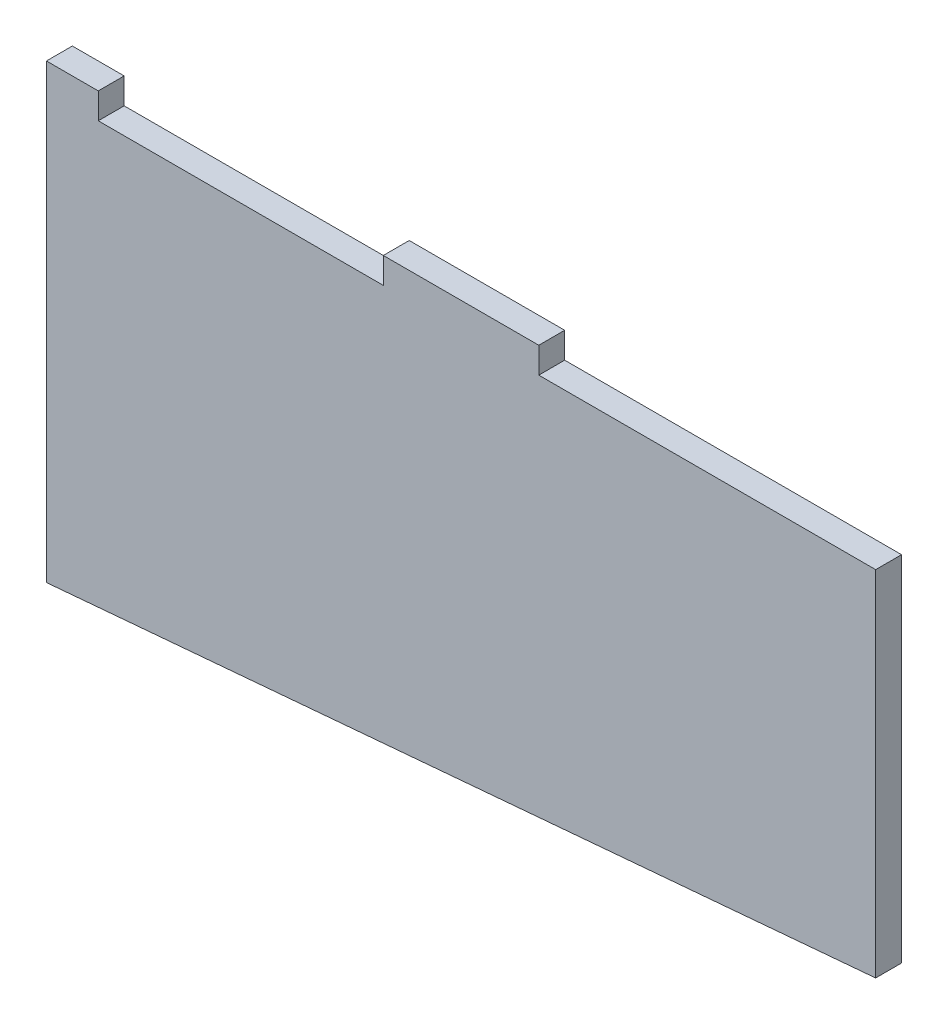
SolidWorks part; units mm, degrees
ref_plane "Front Plane" through (0, 0, 0) normal (0, 0, 1) x (1, 0, 0)
ref_plane "Top Plane" through (0, 0, 0) normal (0, 1, 0) x (1, 0, 0)
ref_plane "Right Plane" through (0, 0, 0) normal (1, 0, 0) x (0, 0, -1)
sketch "Sketch1" plane through (0, 0, 0) normal (0, 0, 1) x (1, 0, 0)
  line L0 (0, 0) -> (12.7, 0)
  line L4 (12.7, 0) -> (12.7, -6.35)
  line L5 (12.7, -6.35) -> (82.55, -6.35)
  line L6 (82.55, -6.35) -> (82.55, 0)
  line L7 (82.55, 0) -> (120.65, 0)
  line L8 (120.65, 0) -> (120.65, -6.35)
  line L9 (120.65, -6.35) -> (203.2, -6.35)
  line L10 (203.2, -6.35) -> (203.2, -93.0139)
  line L11 (203.2, -93.0139) -> (0, -110.6942)
  line L12 (0, -110.6942) -> (0, 0)
  point P5 (0, 0)
  dimension "D1" = 12.7
  dimension "D2" = 6.35
  dimension "D3" = 69.85
  dimension "D4" = 38.1
  dimension "D5" = 82.55
extrude "Boss-Extrude1" add sketch "Sketch1" along normal blind 6.35
